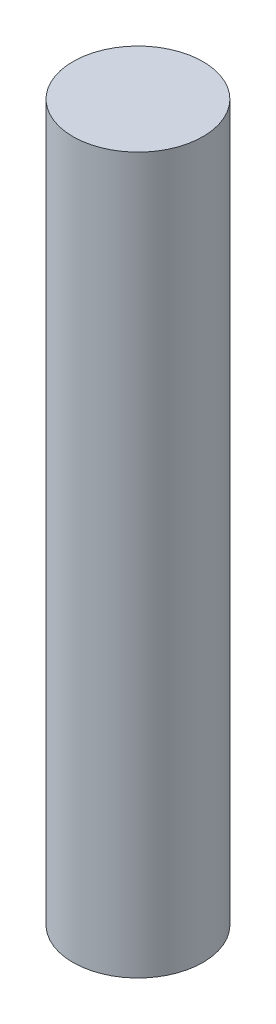
SolidWorks part; units mm, degrees
ref_plane "Plan de face" through (0, 0, 0) normal (0, 0, 1) x (1, 0, 0)
ref_plane "Plan de dessus" through (0, 0, 0) normal (0, 1, 0) x (1, 0, 0)
ref_plane "Plan de droite" through (0, 0, 0) normal (1, 0, 0) x (0, 0, -1)
sketch "Esquisse1" plane through (0, 0, 0) normal (0, 1, 0) x (1, 0, 0)
  circle A0 centre (0, 0) radius 1
  dimension "D1" = 2
extrude "Boss.-Extru.2" add sketch "Esquisse1" along normal blind 11 contours A0
